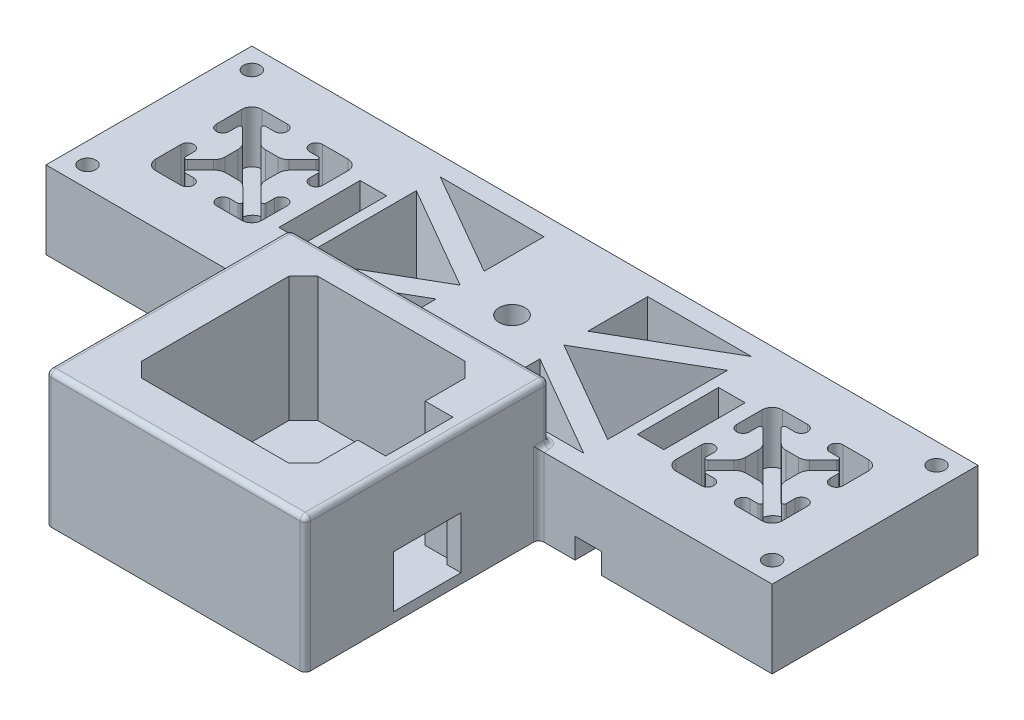
SolidWorks part; units mm, degrees
ref_plane "Front" through (0, 0, 0) normal (0, 0, 1) x (1, 0, 0)
ref_plane "Top" through (0, 0, 0) normal (0, 1, 0) x (1, 0, 0)
ref_plane "Right" through (0, 0, 0) normal (1, 0, 0) x (0, 0, -1)
sketch "Sketch1" plane through (0, 0, 0) normal (0, 1, 0) x (1, 0, 0)
  line L1 (0, 0) -> (177.8, 0)
  line L2 (0, 0) -> (0, 50.4)
  line L3 (0, 50.4) -> (177.8, 50.4)
  line L4 (177.8, 0) -> (177.8, 50.4)
  dimension "D1" = 177.8
  dimension "D2" = 50.4
extrude "Boss-Extrude1" add sketch "Sketch1" along normal blind 6.35
sketch "Sketch2" plane through (0, 6.35, 0) normal (0, 1, 0) x (1, 0, 0)
  line L0 (37.6996, 29.52) -> (37.6996, 35.7372) construction
  line L1 (35.7368, 37.7) -> (29.5196, 37.7) construction
  line L2 (29.5196, 35.56) -> (31.619, 35.56) construction
  line L3 (32.3326, 33.8353) -> (28.9966, 30.504) construction
  line L4 (26.7566, 29.5771) -> (23.643, 29.5771) construction
  line L5 (21.403, 30.504) -> (18.067, 33.8353) construction
  line L6 (18.7806, 35.56) -> (20.88, 35.56) construction
  line L7 (20.88, 37.7) -> (14.6628, 37.7) construction
  line L8 (12.7, 35.7372) -> (12.7, 29.52) construction
  line L9 (14.84, 29.52) -> (14.84, 31.5965) construction
  line L10 (16.5637, 32.3112) -> (19.7659, 29.1135) construction
  line L11 (20.743, 26.7568) -> (20.743, 23.6432) construction
  line L12 (19.7659, 21.2865) -> (16.5637, 18.0888) construction
  line L13 (14.84, 18.8035) -> (14.84, 20.88) construction
  line L14 (12.7, 20.88) -> (12.7, 14.6628) construction
  line L15 (14.6628, 12.7) -> (20.8121, 12.7) construction
  line L16 (20.8121, 14.84) -> (18.7806, 14.84) construction
  line L17 (18.067, 16.5647) -> (21.403, 19.896) construction
  line L18 (23.643, 20.8229) -> (26.7566, 20.8229) construction
  line L19 (28.9966, 19.896) -> (32.3326, 16.5647) construction
  line L20 (31.619, 14.84) -> (29.5875, 14.84) construction
  line L21 (29.5875, 12.7) -> (35.7368, 12.7) construction
  line L22 (37.6996, 14.6628) -> (37.6996, 20.88) construction
  line L23 (35.5596, 20.88) -> (35.5596, 18.8035) construction
  line L24 (33.8359, 18.0888) -> (30.6337, 21.2865) construction
  line L25 (29.6566, 23.6432) -> (29.6566, 26.7568) construction
  line L26 (30.6337, 29.1135) -> (33.8359, 32.3112) construction
  line L27 (35.5596, 31.5965) -> (35.5596, 29.52) construction
  line L28 (0, 50.4) -> (0, 0) construction
  line L29 (177.8, 50.4) -> (0, 50.4) construction
  line L30 (0, 0) -> (177.8, 0) construction
  line L31 (88.9, 50.4) -> (88.9, 0) construction
  line L32 (142.2404, 31.5965) -> (142.2404, 29.52) construction
  line L33 (147.1663, 29.1135) -> (143.9641, 32.3112) construction
  line L34 (148.1434, 23.6432) -> (148.1434, 26.7568) construction
  line L35 (143.9641, 18.0888) -> (147.1663, 21.2865) construction
  line L36 (142.2404, 20.88) -> (142.2404, 18.8035) construction
  line L37 (140.1004, 14.6628) -> (140.1004, 20.88) construction
  line L38 (148.2125, 12.7) -> (142.0632, 12.7) construction
  line L39 (146.181, 14.84) -> (148.2125, 14.84) construction
  line L40 (148.8034, 19.896) -> (145.4674, 16.5647) construction
  line L41 (154.157, 20.8229) -> (151.0434, 20.8229) construction
  line L42 (159.733, 16.5647) -> (156.397, 19.896) construction
  line L43 (156.9879, 14.84) -> (159.0194, 14.84) construction
  line L44 (163.1372, 12.7) -> (156.9879, 12.7) construction
  line L45 (165.1, 20.88) -> (165.1, 14.6628) construction
  line L46 (162.96, 18.8035) -> (162.96, 20.88) construction
  line L47 (158.0341, 21.2865) -> (161.2363, 18.0888) construction
  line L48 (157.057, 26.7568) -> (157.057, 23.6432) construction
  line L49 (161.2363, 32.3112) -> (158.0341, 29.1135) construction
  line L50 (162.96, 29.52) -> (162.96, 31.5965) construction
  line L51 (165.1, 35.7372) -> (165.1, 29.52) construction
  line L52 (156.92, 37.7) -> (163.1372, 37.7) construction
  line L53 (159.0194, 35.56) -> (156.92, 35.56) construction
  line L54 (156.397, 30.504) -> (159.733, 33.8353) construction
  line L55 (151.0434, 29.5771) -> (154.157, 29.5771) construction
  line L56 (145.4674, 33.8353) -> (148.8034, 30.504) construction
  line L57 (148.2804, 35.56) -> (146.181, 35.56) construction
  line L58 (142.0632, 37.7) -> (148.2804, 37.7) construction
  line L59 (140.1004, 29.52) -> (140.1004, 35.7372) construction
  line L60 (38.2076, 29.52) -> (38.2076, 35.7372)
  line L62 (0, 50.4) -> (0, 0)
  line L63 (0, 0) -> (177.8, 0)
  line L64 (177.8, 50.4) -> (177.8, 0)
  line L65 (35.7368, 38.208) -> (29.5196, 38.208)
  line L66 (29.5196, 35.052) -> (31.619, 35.052)
  line L67 (31.9737, 34.1948) -> (28.6376, 30.8635)
  line L68 (26.7566, 30.0851) -> (23.643, 30.0851)
  line L69 (21.762, 30.8635) -> (18.4259, 34.1948)
  line L70 (18.7806, 35.052) -> (20.88, 35.052)
  line L71 (20.88, 38.208) -> (14.6628, 38.208)
  line L72 (12.192, 35.7372) -> (12.192, 29.52)
  line L73 (15.348, 29.52) -> (15.348, 31.5965)
  line L74 (16.2047, 31.9517) -> (19.4069, 28.7541)
  line L75 (20.235, 26.7568) -> (20.235, 23.6432)
  line L76 (19.4069, 21.6459) -> (16.2047, 18.4483)
  line L77 (15.348, 18.8035) -> (15.348, 20.88)
  line L78 (12.192, 20.88) -> (12.192, 14.6628)
  line L79 (14.6628, 12.192) -> (20.8121, 12.192)
  line L80 (20.8121, 15.348) -> (18.7806, 15.348)
  line L81 (18.4259, 16.2052) -> (21.762, 19.5365)
  line L82 (23.643, 20.3149) -> (26.7566, 20.3149)
  line L83 (28.6376, 19.5365) -> (31.9737, 16.2052)
  line L84 (31.619, 15.348) -> (29.5875, 15.348)
  line L85 (29.5875, 12.192) -> (35.7368, 12.192)
  line L86 (38.2076, 14.6628) -> (38.2076, 20.88)
  line L87 (35.0516, 20.88) -> (35.0516, 18.8035)
  line L88 (34.1949, 18.4483) -> (30.9927, 21.6459)
  line L89 (30.1646, 23.6432) -> (30.1646, 26.7568)
  line L90 (30.9927, 28.7541) -> (34.1949, 31.9517)
  line L91 (35.0516, 31.5965) -> (35.0516, 29.52)
  line L92 (142.7484, 31.5965) -> (142.7484, 29.52)
  line L93 (139.5924, 29.52) -> (139.5924, 35.7372)
  line L94 (142.0632, 38.208) -> (148.2804, 38.208)
  line L95 (148.2804, 35.052) -> (146.181, 35.052)
  line L96 (145.8263, 34.1948) -> (149.1624, 30.8635)
  line L97 (151.0434, 30.0851) -> (154.157, 30.0851)
  line L98 (156.038, 30.8635) -> (159.3741, 34.1948)
  line L99 (159.0194, 35.052) -> (156.92, 35.052)
  line L100 (156.92, 38.208) -> (163.1372, 38.208)
  line L101 (165.608, 35.7372) -> (165.608, 29.52)
  line L102 (162.452, 29.52) -> (162.452, 31.5965)
  line L103 (161.5953, 31.9517) -> (158.3931, 28.7541)
  line L104 (157.565, 26.7568) -> (157.565, 23.6432)
  line L105 (158.3931, 21.6459) -> (161.5953, 18.4483)
  line L106 (162.452, 18.8035) -> (162.452, 20.88)
  line L107 (165.608, 20.88) -> (165.608, 14.6628)
  line L108 (163.1372, 12.192) -> (156.9879, 12.192)
  line L109 (156.9879, 15.348) -> (159.0194, 15.348)
  line L110 (159.3741, 16.2052) -> (156.038, 19.5365)
  line L111 (154.157, 20.3149) -> (151.0434, 20.3149)
  line L112 (149.1624, 19.5365) -> (145.8263, 16.2052)
  line L113 (146.181, 15.348) -> (148.2125, 15.348)
  line L114 (148.2125, 12.192) -> (142.0632, 12.192)
  line L115 (139.5924, 14.6628) -> (139.5924, 20.88)
  line L116 (142.7484, 20.88) -> (142.7484, 18.8035)
  line L117 (143.6051, 18.4483) -> (146.8073, 21.6459)
  line L118 (147.6354, 23.6432) -> (147.6354, 26.7568)
  line L119 (146.8073, 28.7541) -> (143.6051, 31.9517)
  line L120 (177.8, 50.4) -> (0, 50.4)
  arc A1 (37.6996, 35.7372) -> (35.7368, 37.7) centre (35.7368, 35.7372) ccw construction
  arc A2 (29.5196, 37.7) -> (29.5196, 35.56) centre (29.5196, 36.63) ccw construction
  arc A3 (31.619, 35.56) -> (32.3326, 33.8353) centre (31.619, 34.55) cw construction
  arc A4 (28.9966, 30.504) -> (26.7566, 29.5771) centre (26.7566, 32.7471) cw construction
  arc A5 (23.643, 29.5771) -> (21.403, 30.504) centre (23.643, 32.7471) cw construction
  arc A6 (18.067, 33.8353) -> (18.7806, 35.56) centre (18.7806, 34.55) cw construction
  arc A7 (20.88, 35.56) -> (20.88, 37.7) centre (20.88, 36.63) ccw construction
  arc A8 (14.6628, 37.7) -> (12.7, 35.7372) centre (14.6628, 35.7372) ccw construction
  arc A9 (12.7, 29.52) -> (14.84, 29.52) centre (13.77, 29.52) ccw construction
  arc A10 (14.84, 31.5965) -> (16.5637, 32.3112) centre (15.85, 31.5965) cw construction
  arc A11 (19.7659, 29.1135) -> (20.743, 26.7568) centre (17.4126, 26.7568) cw construction
  arc A12 (20.743, 23.6432) -> (19.7659, 21.2865) centre (17.4126, 23.6432) cw construction
  arc A13 (16.5637, 18.0888) -> (14.84, 18.8035) centre (15.85, 18.8035) cw construction
  arc A14 (14.84, 20.88) -> (12.7, 20.88) centre (13.77, 20.88) ccw construction
  arc A15 (12.7, 14.6628) -> (14.6628, 12.7) centre (14.6628, 14.6628) ccw construction
  arc A16 (20.8121, 12.7) -> (20.8121, 14.84) centre (20.8121, 13.77) ccw construction
  arc A17 (18.7806, 14.84) -> (18.067, 16.5647) centre (18.7806, 15.85) cw construction
  arc A18 (21.403, 19.896) -> (23.643, 20.8229) centre (23.643, 17.6529) cw construction
  arc A19 (26.7566, 20.8229) -> (28.9966, 19.896) centre (26.7566, 17.6529) cw construction
  arc A20 (32.3326, 16.5647) -> (31.619, 14.84) centre (31.619, 15.85) cw construction
  arc A21 (29.5875, 14.84) -> (29.5875, 12.7) centre (29.5875, 13.77) ccw construction
  arc A22 (35.7368, 12.7) -> (37.6996, 14.6628) centre (35.7368, 14.6628) ccw construction
  arc A23 (37.6996, 20.88) -> (35.5596, 20.88) centre (36.6296, 20.88) ccw construction
  arc A24 (35.5596, 18.8035) -> (33.8359, 18.0888) centre (34.5496, 18.8035) cw construction
  arc A25 (30.6337, 21.2865) -> (29.6566, 23.6432) centre (32.987, 23.6432) cw construction
  arc A26 (29.6566, 26.7568) -> (30.6337, 29.1135) centre (32.987, 26.7568) cw construction
  arc A27 (33.8359, 32.3112) -> (35.5596, 31.5965) centre (34.5496, 31.5965) cw construction
  arc A28 (35.5596, 29.52) -> (37.6996, 29.52) centre (36.6296, 29.52) ccw construction
  arc A29 (142.2404, 29.52) -> (140.1004, 29.52) centre (141.1704, 29.52) cw construction
  arc A30 (143.9641, 32.3112) -> (142.2404, 31.5965) centre (143.2504, 31.5965) ccw construction
  arc A31 (148.1434, 26.7568) -> (147.1663, 29.1135) centre (144.813, 26.7568) ccw construction
  arc A32 (147.1663, 21.2865) -> (148.1434, 23.6432) centre (144.813, 23.6432) ccw construction
  arc A33 (142.2404, 18.8035) -> (143.9641, 18.0888) centre (143.2504, 18.8035) ccw construction
  arc A34 (140.1004, 20.88) -> (142.2404, 20.88) centre (141.1704, 20.88) cw construction
  arc A35 (142.0632, 12.7) -> (140.1004, 14.6628) centre (142.0632, 14.6628) cw construction
  arc A36 (148.2125, 14.84) -> (148.2125, 12.7) centre (148.2125, 13.77) cw construction
  arc A37 (145.4674, 16.5647) -> (146.181, 14.84) centre (146.181, 15.85) ccw construction
  arc A38 (151.0434, 20.8229) -> (148.8034, 19.896) centre (151.0434, 17.6529) ccw construction
  arc A39 (156.397, 19.896) -> (154.157, 20.8229) centre (154.157, 17.6529) ccw construction
  arc A40 (159.0194, 14.84) -> (159.733, 16.5647) centre (159.0194, 15.85) ccw construction
  arc A41 (156.9879, 12.7) -> (156.9879, 14.84) centre (156.9879, 13.77) cw construction
  arc A42 (165.1, 14.6628) -> (163.1372, 12.7) centre (163.1372, 14.6628) cw construction
  arc A43 (162.96, 20.88) -> (165.1, 20.88) centre (164.03, 20.88) cw construction
  arc A44 (161.2363, 18.0888) -> (162.96, 18.8035) centre (161.95, 18.8035) ccw construction
  arc A45 (157.057, 23.6432) -> (158.0341, 21.2865) centre (160.3874, 23.6432) ccw construction
  arc A46 (158.0341, 29.1135) -> (157.057, 26.7568) centre (160.3874, 26.7568) ccw construction
  arc A47 (162.96, 31.5965) -> (161.2363, 32.3112) centre (161.95, 31.5965) ccw construction
  arc A48 (165.1, 29.52) -> (162.96, 29.52) centre (164.03, 29.52) cw construction
  arc A49 (163.1372, 37.7) -> (165.1, 35.7372) centre (163.1372, 35.7372) cw construction
  arc A50 (156.92, 35.56) -> (156.92, 37.7) centre (156.92, 36.63) cw construction
  arc A51 (159.733, 33.8353) -> (159.0194, 35.56) centre (159.0194, 34.55) ccw construction
  arc A52 (154.157, 29.5771) -> (156.397, 30.504) centre (154.157, 32.7471) ccw construction
  arc A53 (148.8034, 30.504) -> (151.0434, 29.5771) centre (151.0434, 32.7471) ccw construction
  arc A54 (146.181, 35.56) -> (145.4674, 33.8353) centre (146.181, 34.55) ccw construction
  arc A55 (148.2804, 37.7) -> (148.2804, 35.56) centre (148.2804, 36.63) cw construction
  arc A56 (140.1004, 35.7372) -> (142.0632, 37.7) centre (142.0632, 35.7372) cw construction
  arc A58 (38.2076, 35.7372) -> (35.7368, 38.208) centre (35.7368, 35.7372) ccw
  arc A59 (29.5196, 38.208) -> (29.5196, 35.052) centre (29.5196, 36.63) ccw
  arc A60 (31.619, 35.052) -> (31.9737, 34.1948) centre (31.619, 34.55) cw
  arc A61 (28.6376, 30.8635) -> (26.7566, 30.0851) centre (26.7566, 32.7471) cw
  arc A62 (23.643, 30.0851) -> (21.762, 30.8635) centre (23.643, 32.7471) cw
  arc A63 (18.4259, 34.1948) -> (18.7806, 35.052) centre (18.7806, 34.55) cw
  arc A64 (20.88, 35.052) -> (20.88, 38.208) centre (20.88, 36.63) ccw
  arc A65 (14.6628, 38.208) -> (12.192, 35.7372) centre (14.6628, 35.7372) ccw
  arc A66 (12.192, 29.52) -> (15.348, 29.52) centre (13.77, 29.52) ccw
  arc A67 (15.348, 31.5965) -> (16.2047, 31.9517) centre (15.85, 31.5965) cw
  arc A68 (19.4069, 28.7541) -> (20.235, 26.7568) centre (17.4126, 26.7568) cw
  arc A69 (20.235, 23.6432) -> (19.4069, 21.6459) centre (17.4126, 23.6432) cw
  arc A70 (16.2047, 18.4483) -> (15.348, 18.8035) centre (15.85, 18.8035) cw
  arc A71 (15.348, 20.88) -> (12.192, 20.88) centre (13.77, 20.88) ccw
  arc A72 (12.192, 14.6628) -> (14.6628, 12.192) centre (14.6628, 14.6628) ccw
  arc A73 (20.8121, 12.192) -> (20.8121, 15.348) centre (20.8121, 13.77) ccw
  arc A74 (18.7806, 15.348) -> (18.4259, 16.2052) centre (18.7806, 15.85) cw
  arc A75 (21.762, 19.5365) -> (23.643, 20.3149) centre (23.643, 17.6529) cw
  arc A76 (26.7566, 20.3149) -> (28.6376, 19.5365) centre (26.7566, 17.6529) cw
  arc A77 (31.9737, 16.2052) -> (31.619, 15.348) centre (31.619, 15.85) cw
  arc A78 (29.5875, 15.348) -> (29.5875, 12.192) centre (29.5875, 13.77) ccw
  arc A79 (35.7368, 12.192) -> (38.2076, 14.6628) centre (35.7368, 14.6628) ccw
  arc A80 (38.2076, 20.88) -> (35.0516, 20.88) centre (36.6296, 20.88) ccw
  arc A81 (35.0516, 18.8035) -> (34.1949, 18.4483) centre (34.5496, 18.8035) cw
  arc A82 (30.9927, 21.6459) -> (30.1646, 23.6432) centre (32.987, 23.6432) cw
  arc A83 (30.1646, 26.7568) -> (30.9927, 28.7541) centre (32.987, 26.7568) cw
  arc A84 (34.1949, 31.9517) -> (35.0516, 31.5965) centre (34.5496, 31.5965) cw
  arc A85 (35.0516, 29.52) -> (38.2076, 29.52) centre (36.6296, 29.52) ccw
  arc A86 (142.7484, 29.52) -> (139.5924, 29.52) centre (141.1704, 29.52) cw
  arc A87 (139.5924, 35.7372) -> (142.0632, 38.208) centre (142.0632, 35.7372) cw
  arc A88 (148.2804, 38.208) -> (148.2804, 35.052) centre (148.2804, 36.63) cw
  arc A89 (146.181, 35.052) -> (145.8263, 34.1948) centre (146.181, 34.55) ccw
  arc A90 (149.1624, 30.8635) -> (151.0434, 30.0851) centre (151.0434, 32.7471) ccw
  arc A91 (154.157, 30.0851) -> (156.038, 30.8635) centre (154.157, 32.7471) ccw
  arc A92 (159.3741, 34.1948) -> (159.0194, 35.052) centre (159.0194, 34.55) ccw
  arc A93 (156.92, 35.052) -> (156.92, 38.208) centre (156.92, 36.63) cw
  arc A94 (163.1372, 38.208) -> (165.608, 35.7372) centre (163.1372, 35.7372) cw
  arc A95 (165.608, 29.52) -> (162.452, 29.52) centre (164.03, 29.52) cw
  arc A96 (162.452, 31.5965) -> (161.5953, 31.9517) centre (161.95, 31.5965) ccw
  arc A97 (158.3931, 28.7541) -> (157.565, 26.7568) centre (160.3874, 26.7568) ccw
  arc A98 (157.565, 23.6432) -> (158.3931, 21.6459) centre (160.3874, 23.6432) ccw
  arc A99 (161.5953, 18.4483) -> (162.452, 18.8035) centre (161.95, 18.8035) ccw
  arc A100 (162.452, 20.88) -> (165.608, 20.88) centre (164.03, 20.88) cw
  arc A101 (165.608, 14.6628) -> (163.1372, 12.192) centre (163.1372, 14.6628) cw
  arc A102 (156.9879, 12.192) -> (156.9879, 15.348) centre (156.9879, 13.77) cw
  arc A103 (159.0194, 15.348) -> (159.3741, 16.2052) centre (159.0194, 15.85) ccw
  arc A104 (156.038, 19.5365) -> (154.157, 20.3149) centre (154.157, 17.6529) ccw
  arc A105 (151.0434, 20.3149) -> (149.1624, 19.5365) centre (151.0434, 17.6529) ccw
  arc A106 (145.8263, 16.2052) -> (146.181, 15.348) centre (146.181, 15.85) ccw
  arc A107 (148.2125, 15.348) -> (148.2125, 12.192) centre (148.2125, 13.77) cw
  arc A108 (142.0632, 12.192) -> (139.5924, 14.6628) centre (142.0632, 14.6628) cw
  arc A109 (139.5924, 20.88) -> (142.7484, 20.88) centre (141.1704, 20.88) cw
  arc A110 (142.7484, 18.8035) -> (143.6051, 18.4483) centre (143.2504, 18.8035) ccw
  arc A111 (146.8073, 21.6459) -> (147.6354, 23.6432) centre (144.813, 23.6432) ccw
  arc A112 (147.6354, 26.7568) -> (146.8073, 28.7541) centre (144.813, 26.7568) ccw
  arc A113 (143.6051, 31.9517) -> (142.7484, 31.5965) centre (143.2504, 31.5965) ccw
  dimension "D2" = 1.07
  dimension "D3" = 3.17
  dimension "D4" = 3.3305
  dimension "D8" = 1.9628
  dimension "D9" = 1.01
  dimension "D5" = 12.7
  dimension "D6" = 12.7
  dimension "D7" = 12.7
  dimension "D10" = 16.5637
  dimension "D12" = 0.508
  dimension "D13" = 0.508
extrude "Boss-Extrude2" add sketch "Sketch2" along normal blind 12.7
sketch "Sketch3" plane through (0, 19.05, 0) normal (0, 1, 0) x (1, 0, 0)
  line L0 (177.8, 50.4) -> (0, 50.4) construction
  line L1 (0, 50.4) -> (0, 0) construction
  circle A0 centre (88.9, 25.2) radius 3.175
  point P4 (88.9, 50.4)
  point P7 (0, 25.2)
  dimension "D1" = 6.35
extrude "Cut-Extrude1" cut sketch "Sketch3" against normal through all
sketch "Sketch4" plane through (0, 19.05, 0) normal (0, 1, 0) x (1, 0, 0)
  line L0 (50.8, 45.7306) -> (76.2, 45.7306)
  line L1 (76.2, 45.7306) -> (76.2, 31.0659)
  line L2 (76.2, 31.0659) -> (50.8, 45.7306)
  line L3 (76.2, 19.3341) -> (76.2, 4.6694)
  line L4 (76.2, 4.6694) -> (50.8, 4.6694)
  line L5 (50.8, 4.6694) -> (76.2, 19.3341)
  line L6 (50.8, 39.8647) -> (50.8, 10.5353)
  line L7 (50.8, 10.5353) -> (76.2, 25.2)
  line L8 (76.2, 25.2) -> (50.8, 39.8647)
  line L9 (0, 50.4) -> (0, 0) construction
  line L10 (88.9, 50.4) -> (88.9, 0) construction
  line L11 (177.8, 50.4) -> (0, 50.4) construction
  line L12 (0, 0) -> (177.8, 0) construction
  line L13 (101.6, 25.2) -> (127, 39.8647)
  line L14 (127, 10.5353) -> (101.6, 25.2)
  line L15 (127, 39.8647) -> (127, 10.5353)
  line L16 (127, 4.6694) -> (101.6, 19.3341)
  line L17 (101.6, 4.6694) -> (127, 4.6694)
  line L18 (101.6, 19.3341) -> (101.6, 4.6694)
  line L19 (101.6, 31.0659) -> (127, 45.7306)
  line L20 (101.6, 45.7306) -> (101.6, 31.0659)
  line L21 (127, 45.7306) -> (101.6, 45.7306)
  point P18 (88.9, 25.2)
  dimension "D1" = 25.4
  dimension "D2" = 25.4
  dimension "D3" = 50.8
  dimension "D4" = 5.08
  dimension "D5" = 5.08
  dimension "D7" = 60
extrude "Cut-Extrude2" cut sketch "Sketch4" against normal through all
sketch "Sketch5" plane through (0, 19.05, 0) normal (0, 1, 0) x (1, 0, 0)
  line L0 (0, 50.4) -> (0, 0) construction
  line L1 (41.7636, 35.15) -> (48.2636, 35.15)
  line L2 (41.7636, 35.15) -> (41.7636, 15.25)
  line L3 (41.7636, 15.25) -> (48.2636, 15.25)
  line L4 (48.2636, 35.15) -> (48.2636, 15.25)
  line L5 (38.2076, 29.52) -> (38.2076, 35.7372) construction
  point P6 (0, 25.2)
  point P7 (48.2636, 25.2)
  dimension "D1" = 6.5
  dimension "D2" = 19.9
  dimension "D3" = 3.556
extrude "Cut-Extrude3" cut sketch "Sketch5" against normal blind 10.2
sketch "Sketch6" plane through (0, 8.85, 0) normal (0, 1, 0) x (1, 0, 0)
  line L0 (48.2636, 15.25) -> (48.2636, 35.15) construction
  line L1 (41.7636, 35.15) -> (48.2636, 35.15)
  line L2 (41.7636, 35.15) -> (41.7636, 30.578)
  line L3 (41.7636, 30.578) -> (48.2636, 30.578)
  line L4 (48.2636, 35.15) -> (48.2636, 30.578)
  line L5 (41.7636, 35.15) -> (41.7636, 15.25) construction
  line L6 (48.2636, 15.25) -> (48.2636, 35.15) construction
  line L7 (41.7636, 27.486) -> (48.2636, 27.486)
  line L8 (41.7636, 27.486) -> (41.7636, 22.914)
  line L9 (41.7636, 22.914) -> (48.2636, 22.914)
  line L10 (48.2636, 27.486) -> (48.2636, 22.914)
  line L12 (41.7636, 15.25) -> (48.2636, 15.25)
  line L13 (41.7636, 15.25) -> (41.7636, 19.822)
  line L14 (41.7636, 19.822) -> (48.2636, 19.822)
  line L15 (48.2636, 15.25) -> (48.2636, 19.822)
  line L16 (41.7636, 25.2) -> (0, 25.2) construction
  line L17 (0, 50.4) -> (0, 0) construction
  dimension "D1" = 4.572
extrude "Cut-Extrude4" cut sketch "Sketch6" against normal through all
ref_plane "Plane1" through (88.9, 0, 0) normal (-1, 0, 0) x (0, 0, 1)
mirror "Mirror1" about plane through (88.9, 0, 0) normal (-1, 0, 0) of "Cut-Extrude4", "Cut-Extrude3"
sketch "Sketch7" plane through (0, 6.35, 0) normal (0, 1, 0) x (1, 0, 0)
  line L0 (26.7566, 30.0851) -> (23.643, 30.0851) construction
  line L1 (30.1646, 23.6432) -> (30.1646, 26.7568) construction
  circle A0 centre (25.3386, 25.2591) radius 2.921
  dimension "D1" = 5.842
  dimension "D2" = 4.826
  dimension "D3" = 4.826
extrude "Cut-Extrude5" cut sketch "Sketch7" against normal through all both and the other way through all
sketch "Sketch8" plane through (0, 6.35, 0) normal (0, 1, 0) x (1, 0, 0)
  line L0 (154.157, 30.0851) -> (151.0434, 30.0851) construction
  line L1 (157.565, 23.6432) -> (157.565, 26.7568) construction
  circle A0 centre (152.739, 25.2591) radius 2.921
  dimension "D1" = 5.842
  dimension "D2" = 4.826
  dimension "D3" = 4.826
extrude "Cut-Extrude6" cut sketch "Sketch8" against normal through all both and the other way through all
chamfer "Chamfer2" distance 3.302 angle 45 1 edges at (152.739, 0, -22.3381)
chamfer "Chamfer3" distance 3.302 angle 45 1 edges at (25.3386, 0, -22.3381)
sketch "Sketch9" plane through (0, 0, 0) normal (0, 1, 0) x (1, 0, 0)
  line L0 (120.65, 0) -> (120.65, -57.15)
  line L3 (0, 0) -> (177.8, 0) construction
  line L8 (57.15, -57.15) -> (120.65, -57.15)
  line L13 (57.15, 0) -> (57.15, -57.15)
  line L15 (57.15, 0) -> (57.15, 2.54)
  line L16 (57.15, 2.54) -> (120.65, 2.54)
  line L17 (120.65, 0) -> (120.65, 2.54)
  dimension "D1" = 57.15
  dimension "D2" = 63.5
  dimension "D3" = 2.54
sketch "Sketch11" plane through (0, 0, 0) normal (0, 1, 0) x (1, 0, 0)
  line L0 (0, 0) -> (177.8, 0) construction
  line L2 (41.7636, 15.25) -> (41.7636, 0)
  line L3 (41.7636, 0) -> (48.2636, 0)
  line L4 (48.2636, 15.25) -> (48.2636, 0)
  line L5 (48.2636, 15.25) -> (48.2636, 35.15) construction
  line L6 (177.8, 50.4) -> (0, 50.4) construction
  line L8 (41.7636, 35.15) -> (41.7636, 50.4)
  line L9 (41.7636, 50.4) -> (48.2636, 50.4)
  line L10 (48.2636, 35.15) -> (48.2636, 50.4)
  line L11 (41.7636, 35.15) -> (41.7636, 15.25)
  line L12 (48.2636, 35.15) -> (48.2636, 15.25)
  line L13 (88.9, 50.4) -> (88.9, 0) construction
  line L14 (136.0364, 0) -> (129.5364, 0)
  line L15 (136.0364, 50.4) -> (129.5364, 50.4)
  line L16 (129.5364, 15.25) -> (129.5364, 0)
  line L17 (136.0364, 15.25) -> (136.0364, 0)
  line L18 (129.5364, 35.15) -> (129.5364, 15.25)
  line L19 (136.0364, 35.15) -> (136.0364, 15.25)
  line L20 (129.5364, 35.15) -> (129.5364, 50.4)
  line L21 (136.0364, 35.15) -> (136.0364, 50.4)
extrude "Cut-Extrude8" cut sketch "Sketch11" along normal blind 5.08
extrude "Boss-Extrude4" add sketch "Sketch9" along normal blind 33.02
sketch "Sketch12" plane through (0, 33.02, 0) normal (0, 1, 0) x (1, 0, 0)
  line L0 (70.8455, -4.302) -> (106.9545, -4.302)
  line L1 (106.9545, -4.302) -> (110.49, -7.8375)
  line L2 (110.49, -7.8375) -> (110.49, -17.642)
  line L3 (110.49, -43.9465) -> (106.9545, -47.482)
  line L4 (106.9545, -47.482) -> (70.8455, -47.482)
  line L5 (70.8455, -47.482) -> (67.31, -43.9465)
  line L6 (67.31, -43.9465) -> (67.31, -7.8375)
  line L7 (67.31, -7.8375) -> (70.8455, -4.302)
  line L8 (57.15, -57.15) -> (120.65, -57.15) construction
  line L10 (110.49, -34.142) -> (110.49, -43.9465)
  line L11 (110.49, -17.642) -> (117.29, -17.642)
  line L13 (110.49, -34.142) -> (117.29, -34.142)
  line L14 (117.29, -17.642) -> (117.29, -34.142)
  point P10 (88.9, -57.15)
  point P11 (88.9, -47.482)
  point P15 (67.31, -25.892)
  point P21 (117.29, -25.892)
  dimension "D1" = 5
  dimension "D2" = 43.18
  dimension "D3" = 135
  dimension "D4" = 135
  dimension "D5" = 135
  dimension "D6" = 43.18
  dimension "D7" = 16.5
  dimension "D8" = 6.8
extrude "Cut-Extrude9" cut sketch "Sketch12" against normal blind 30.6
sketch "Sketch13" plane through (120.65, 0, 0) normal (1, 0, 0) x (0, 0, -1)
  line L0 (-57.15, 33.02) -> (2.54, 33.02) construction
  line L1 (-35.555, 15.12) -> (-19.055, 15.12)
  line L2 (-35.555, 15.12) -> (-35.555, 2.42)
  line L3 (-35.555, 2.42) -> (-19.055, 2.42)
  line L4 (-19.055, 15.12) -> (-19.055, 2.42)
  point P6 (-27.305, 33.02)
  point P7 (-27.305, 15.12)
  dimension "D1" = 16.5
  dimension "D2" = 12.7
  dimension "D3" = 30.6
extrude "Cut-Extrude10" cut sketch "Sketch13" against normal blind 30.6
fillet "Fillet1" radius 1.27 13 edges at (120.65, 19.05, -1.27) (57.15, 19.05, -1.27) (120.65, 26.035, -2.54) (57.15, 26.035, -2.54) (88.9, 19.05, -2.54) (57.15, 9.525, 0) (120.65, 9.525, 0) (120.65, 33.02, 27.305) (120.65, 16.51, 57.15) (88.9, 33.02, 57.15) (57.15, 33.02, 27.305) (57.15, 16.51, 57.15) (88.9, 33.02, -2.54)
sketch "Sketch14" plane through (0, 2.42, 0) normal (0, 1, 0) x (1, 0, 0)
  line L0 (88.9, -4.302) -> (88.9, -47.482) construction
  line L1 (106.9545, -4.302) -> (70.8455, -4.302) construction
  line L2 (70.8455, -47.482) -> (106.9545, -47.482) construction
  circle A0 centre (88.9, -25.892) radius 2.921
  dimension "D1" = 5.842
extrude "Cut-Extrude11" cut sketch "Sketch14" against normal through all
sketch "Sketch15" plane through (0, 0, 0) normal (0, 1, 0) x (1, 0, 0)
  circle A0 centre (88.9, 25.2) radius 7.62
  dimension "D1" = 15.24
extrude "Cut-Extrude12" cut sketch "Sketch15" along normal blind 8.128
sketch "Sketch16" plane through (0, 19.05, 0) normal (0, 1, 0) x (1, 0, 0)
  line L0 (88.9, 50.4) -> (88.9, -47.482) construction
  line L1 (177.8, 50.4) -> (0, 50.4) construction
  line L2 (70.8455, -47.482) -> (106.9545, -47.482) construction
  line L3 (0, 25.2) -> (177.8, 25.2) construction
  line L4 (0, 50.4) -> (0, 0) construction
  line L5 (177.8, 0) -> (177.8, 50.4) construction
  circle A0 centre (5.08, 45.32) radius 2.032
  circle A1 centre (5.08, 5.08) radius 2.032
  circle A2 centre (172.72, 5.08) radius 2.032
  circle A3 centre (172.72, 45.32) radius 2.032
  dimension "D1" = 4.064
  dimension "D3" = 5.08
  dimension "D2" = 5.08
extrude "Cut-Extrude13" cut sketch "Sketch16" against normal through all
